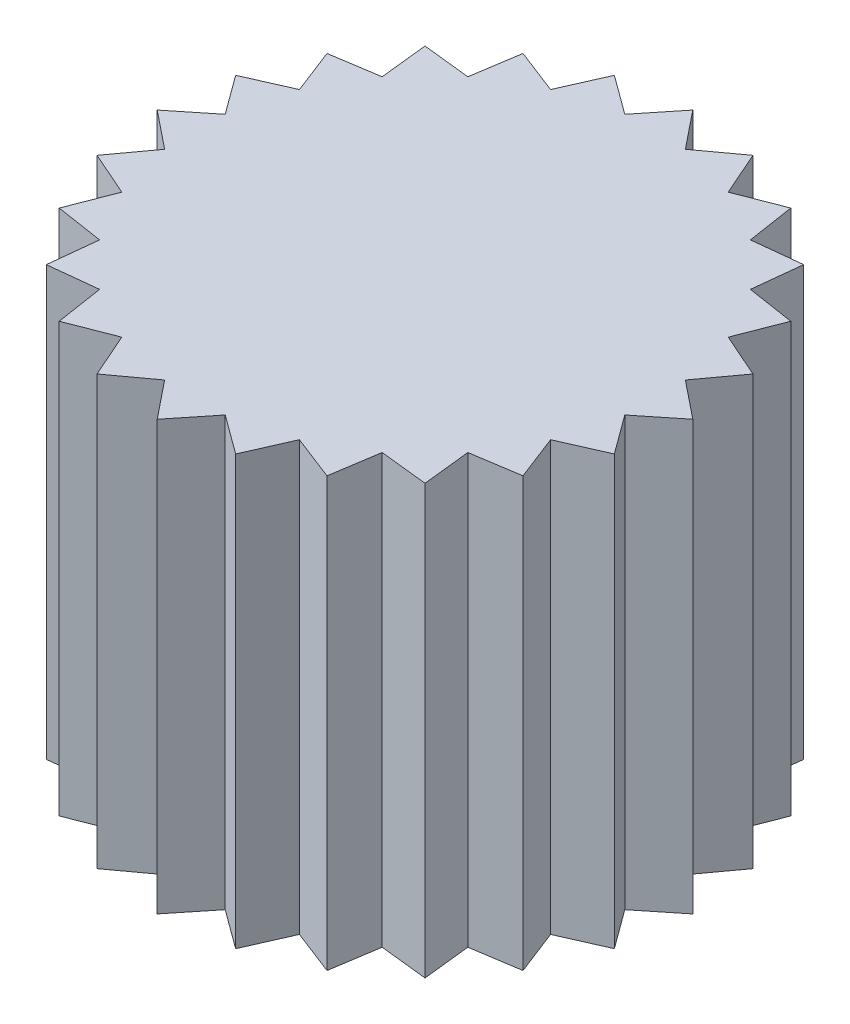
SolidWorks part; units mm, degrees
material "Nylon 6/10"
ref_plane "Front Plane" through (0, 0, 0) normal (0, 0, 1) x (1, 0, 0)
ref_plane "Top Plane" through (0, 0, 0) normal (0, 1, 0) x (1, 0, 0)
ref_plane "Right Plane" through (0, 0, 0) normal (1, 0, 0) x (0, 0, -1)
sketch "Sketch1" plane through (0, 0, 0) normal (0, 1, 0) x (1, 0, 0)
  line L0 (0, 0) -> (0, 1.875) construction
  line L1 (-0.2121, 1.6111) -> (0, 1.875)
  line L2 (-0.2121, 1.6111) -> (-0.6219, 1.5013) construction
  line L3 (-0.6219, 1.5013) -> (-0.9892, 1.2892) construction
  line L4 (-0.9892, 1.2892) -> (-1.2892, 0.9892) construction
  line L5 (-1.2892, 0.9892) -> (-1.5013, 0.6219) construction
  line L6 (-1.5013, 0.6219) -> (-1.6111, 0.2121) construction
  line L7 (-1.6111, 0.2121) -> (-1.6111, -0.2121) construction
  line L8 (-1.6111, -0.2121) -> (-1.5013, -0.6219) construction
  line L9 (-1.5013, -0.6219) -> (-1.2892, -0.9892) construction
  line L10 (-1.2892, -0.9892) -> (-0.9892, -1.2892) construction
  line L11 (-0.9892, -1.2892) -> (-0.6219, -1.5013) construction
  line L12 (-0.6219, -1.5013) -> (-0.2121, -1.6111) construction
  line L13 (-0.2121, -1.6111) -> (0.2121, -1.6111) construction
  line L14 (0.2121, -1.6111) -> (0.6219, -1.5013) construction
  line L15 (0.6219, -1.5013) -> (0.9892, -1.2892) construction
  line L16 (0.9892, -1.2892) -> (1.2892, -0.9892) construction
  line L17 (1.2892, -0.9892) -> (1.5013, -0.6219) construction
  line L18 (1.5013, -0.6219) -> (1.6111, -0.2121) construction
  line L19 (1.6111, -0.2121) -> (1.6111, 0.2121) construction
  line L20 (1.6111, 0.2121) -> (1.5013, 0.6219) construction
  line L21 (1.5013, 0.6219) -> (1.2892, 0.9892) construction
  line L22 (1.2892, 0.9892) -> (0.9892, 1.2892) construction
  line L23 (0.9892, 1.2892) -> (0.6219, 1.5013) construction
  line L24 (0.6219, 1.5013) -> (0.2121, 1.6111) construction
  line L25 (0.2121, 1.6111) -> (-0.2121, 1.6111) construction
  line L26 (0, 1.875) -> (0.2121, 1.6111)
  line L27 (0.2121, 1.6111) -> (0.4853, 1.8111)
  line L28 (0.4853, 1.8111) -> (0.6219, 1.5013)
  line L29 (0.6219, 1.5013) -> (0.9375, 1.6238)
  line L30 (0.9375, 1.6238) -> (0.9892, 1.2892)
  line L31 (0.9892, 1.2892) -> (1.3258, 1.3258)
  line L32 (1.3258, 1.3258) -> (1.2892, 0.9892)
  line L33 (1.2892, 0.9892) -> (1.6238, 0.9375)
  line L34 (1.6238, 0.9375) -> (1.5013, 0.6219)
  line L35 (1.5013, 0.6219) -> (1.8111, 0.4853)
  line L36 (1.8111, 0.4853) -> (1.6111, 0.2121)
  line L37 (1.6111, 0.2121) -> (1.875, 0)
  line L38 (1.875, 0) -> (1.6111, -0.2121)
  line L39 (1.6111, -0.2121) -> (1.8111, -0.4853)
  line L40 (1.8111, -0.4853) -> (1.5013, -0.6219)
  line L41 (1.5013, -0.6219) -> (1.6238, -0.9375)
  line L42 (1.6238, -0.9375) -> (1.2892, -0.9892)
  line L43 (1.2892, -0.9892) -> (1.3258, -1.3258)
  line L44 (1.3258, -1.3258) -> (0.9892, -1.2892)
  line L45 (0.9892, -1.2892) -> (0.9375, -1.6238)
  line L46 (0.9375, -1.6238) -> (0.6219, -1.5013)
  line L47 (0.6219, -1.5013) -> (0.4853, -1.8111)
  line L48 (0.4853, -1.8111) -> (0.2121, -1.6111)
  line L49 (0.2121, -1.6111) -> (0, -1.875)
  line L50 (0, -1.875) -> (-0.2121, -1.6111)
  line L51 (-0.2121, -1.6111) -> (-0.4853, -1.8111)
  line L52 (-0.4853, -1.8111) -> (-0.6219, -1.5013)
  line L53 (-0.6219, -1.5013) -> (-0.9375, -1.6238)
  line L54 (-0.9375, -1.6238) -> (-0.9892, -1.2892)
  line L55 (-0.9892, -1.2892) -> (-1.3258, -1.3258)
  line L56 (-1.3258, -1.3258) -> (-1.2892, -0.9892)
  line L57 (-1.2892, -0.9892) -> (-1.6238, -0.9375)
  line L58 (-1.6238, -0.9375) -> (-1.5013, -0.6219)
  line L59 (-1.5013, -0.6219) -> (-1.8111, -0.4853)
  line L60 (-1.8111, -0.4853) -> (-1.6111, -0.2121)
  line L61 (-1.6111, -0.2121) -> (-1.875, 0)
  line L62 (-1.875, 0) -> (-1.6111, 0.2121)
  line L63 (-1.6111, 0.2121) -> (-1.8111, 0.4853)
  line L64 (-1.8111, 0.4853) -> (-1.5013, 0.6219)
  line L65 (-1.5013, 0.6219) -> (-1.6238, 0.9375)
  line L66 (-1.6238, 0.9375) -> (-1.2892, 0.9892)
  line L67 (-1.2892, 0.9892) -> (-1.3258, 1.3258)
  line L68 (-1.3258, 1.3258) -> (-0.9892, 1.2892)
  line L69 (-0.9892, 1.2892) -> (-0.9375, 1.6238)
  line L70 (-0.9375, 1.6238) -> (-0.6219, 1.5013)
  line L71 (-0.6219, 1.5013) -> (-0.4853, 1.8111)
  line L72 (-0.4853, 1.8111) -> (-0.2121, 1.6111)
  circle A0 centre (0, 0) radius 1.875 construction
  circle A1 centre (0, 0) radius 1.25 construction
  circle A2 centre (0, 0) radius 1.625 construction
  point P4 (0, 1.6111)
  point P102 (0, 0)
  dimension "D1" = 3.75
  dimension "D2" = 2.5
  dimension "D3" = 3.25
extrude "Boss-Extrude1" add sketch "Sketch1" against normal blind 3
ref_axis "Axis1" through (0, 0.15, 0) along (0, -1, 0)
